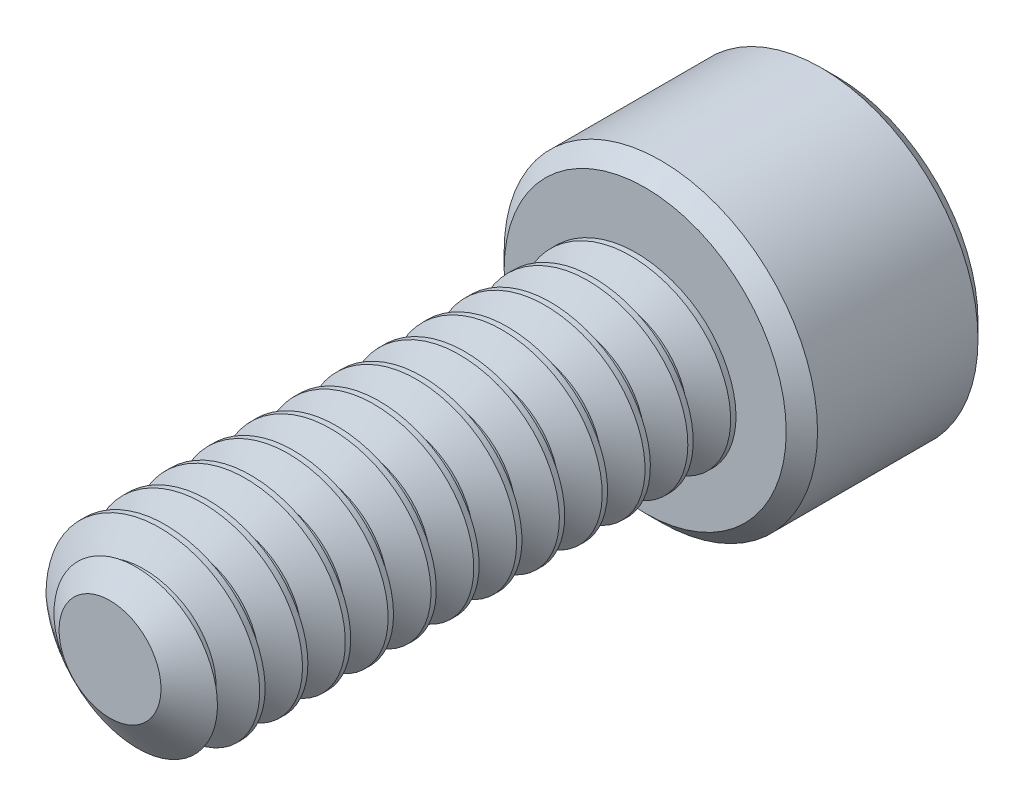
SolidWorks part; units mm, degrees
material "AISI 304"
ref_plane "Front Plane" through (0, 0, 0) normal (0, 0, 1) x (1, 0, 0)
ref_plane "Top Plane" through (0, 0, 0) normal (0, 1, 0) x (1, 0, 0)
ref_plane "Right Plane" through (0, 0, 0) normal (1, 0, 0) x (0, 0, -1)
sketch "Sketch1" plane through (0, 0, 0) normal (0, 0, 1) x (1, 0, 0)
  circle A0 centre (0, 0) radius 1.4224
  dimension "OD" = 2.8448
extrude "Extrude1" add sketch "Sketch1" against normal blind 7.9375
sketch "Sketch2" plane through (0, 0, 0) normal (0, 0, 1) x (1, 0, 0)
  circle A0 centre (0, 0) radius 1.4224 construction
  circle A1 centre (0, 0) radius 1.4224
curve "Helix/Spiral1" pitch 0.635 height 8.5725 radius 1.4224 centre (0, 0, 0) axis (0, 0, -1) start towards (0, 1, 0) parameters "pitch"=0.635
sketch "Sketch3" plane through (0, 0, 0) normal (1, 0, 0) x (0, 0, -1)
  line L0 (-0.5556, 1.4224) -> (-0.3175, 1.01)
  line L1 (-0.3175, 1.01) -> (-0.2381, 1.01)
  line L2 (-0.2381, 1.01) -> (0, 1.4224)
  line L3 (-0.5556, 1.4224) -> (0, 1.4224)
  line L4 (-0.2778, 1.4224) -> (-0.2778, 1.01) construction
  line L5 (-0.4366, 1.2162) -> (-0.1191, 1.2162) construction
  line L6 (0, 1.4224) -> (0, -1.4224) construction
  dimension "D1" = 0.0794
  dimension "D2" = 0.3175
  dimension "D3" = 60
sweep "Cut-Sweep1" cut profiles "Sketch3" path "Helix/Spiral1"
sketch "Sketch4" plane through (0, 0, 0) normal (1, 0, 0) x (0, 0, -1)
  line L0 (0.4666, 1.4224) -> (0, 0.756)
  line L1 (0, 0.756) -> (0, 1.4224)
  line L2 (0.4666, 1.4224) -> (0, 1.4224)
  line L3 (-0.5556, 1.4224) -> (0, 1.4224) construction
  line L4 (0, 0) -> (7.0209, 0) construction
  dimension "D1" = 55
  dimension "D2" = 0.254
revolve "Cut-Revolve1" cut sketch "Sketch4" angle 360 about L4
sketch "Sketch5" plane through (0, 0, 0) normal (1, 0, 0) x (0, 0, -1)
  line L0 (7.9375, -1.0149) -> (7.9375, 1.0232) construction
  line L1 (7.9375, 1.5494) -> (87.4665, 1.5494)
  line L2 (7.9375, 1.5494) -> (7.9375, 0)
  line L3 (7.9375, 0) -> (87.3125, 0)
  line L4 (87.3125, 1.2192) -> (87.3125, 0)
  line L5 (87.4665, 1.5494) -> (87.3125, 1.2192)
  line L6 (0, 0) -> (9.9695, 0) construction
  point P3 (87.3125, 1.5494)
  point P10 (87.3125, 1.5494)
  dimension "D1" = 0.3302
  dimension "Thread min" = 87.3125
  dimension "D2" = 0.127
  dimension "D3" = 25
revolve "partially thread" [suppressed] add sketch "Sketch5" angle 360 about L6
sketch "Sketch6" plane through (0, 0, -7.9375) normal (0, 0, -1) x (-1, 0, 0)
  circle A0 centre (0, 0) radius 2.3241
  dimension "head dia" = 4.6482
extrude "Extrude2" add sketch "Sketch6" along normal blind 2.8448
sketch "Sketch7" plane through (0, 0, -10.7823) normal (0, 0, -1) x (-1, 0, 0)
  line L1 (0, 1.3748) -> (-1.1906, 0.6874)
  line L2 (-1.1906, 0.6874) -> (-1.1906, -0.6874)
  line L3 (-1.1906, -0.6874) -> (0, -1.3748)
  line L4 (0, -1.3748) -> (1.1906, -0.6874)
  line L5 (1.1906, -0.6874) -> (1.1906, 0.6874)
  line L6 (1.1906, 0.6874) -> (0, 1.3748)
  circle A0 centre (0, 0) radius 1.1906 construction
  dimension "hex dia" = 2.3813
extrude "Cut-Extrude1" cut sketch "Sketch7" against normal blind 1.7859
sketch "Sketch8" plane through (0, 0, -10.7823) normal (0, 0, -1) x (-1, 0, 0)
  circle A0 centre (0, 0) radius 1.3748
extrude "Cut-Extrude2" cut sketch "Sketch8" against normal through all draft 45
chamfer "Chamfer1" distance 0.2324 angle 45 2 edges at (-2.3241, 0, -10.7823) (-2.3241, 0, -7.9375)
sketch "Sketch9" plane through (0, 0, 0) normal (1, 0, 0) x (0, 0, -1)
  line L0 (0, 1.4224) -> (0, -1.4224) construction
  line L1 (3.4925, 1.4224) -> (3.4925, -1.4224) construction
  dimension "D1" = 3.4925
equation "\"D3@Helix/Spiral1\" = \"screw length@Extrude1\"+\"pitch@Helix/Spiral1\""
equation "\"D1@Sketch3\" = \"pitch@Helix/Spiral1\"*.125"
equation "\"D2@Sketch3\" = \"pitch@Helix/Spiral1\"*.5"
equation "\"D1@Cut-Extrude1\" = \"hex dia@Sketch7\"*.75"
equation "\"D1@Chamfer1\" = \"head dia@Sketch6\"*.05"
equation "\"D1@Sketch9\" = \"pitch@Helix/Spiral1\"*5.5"
